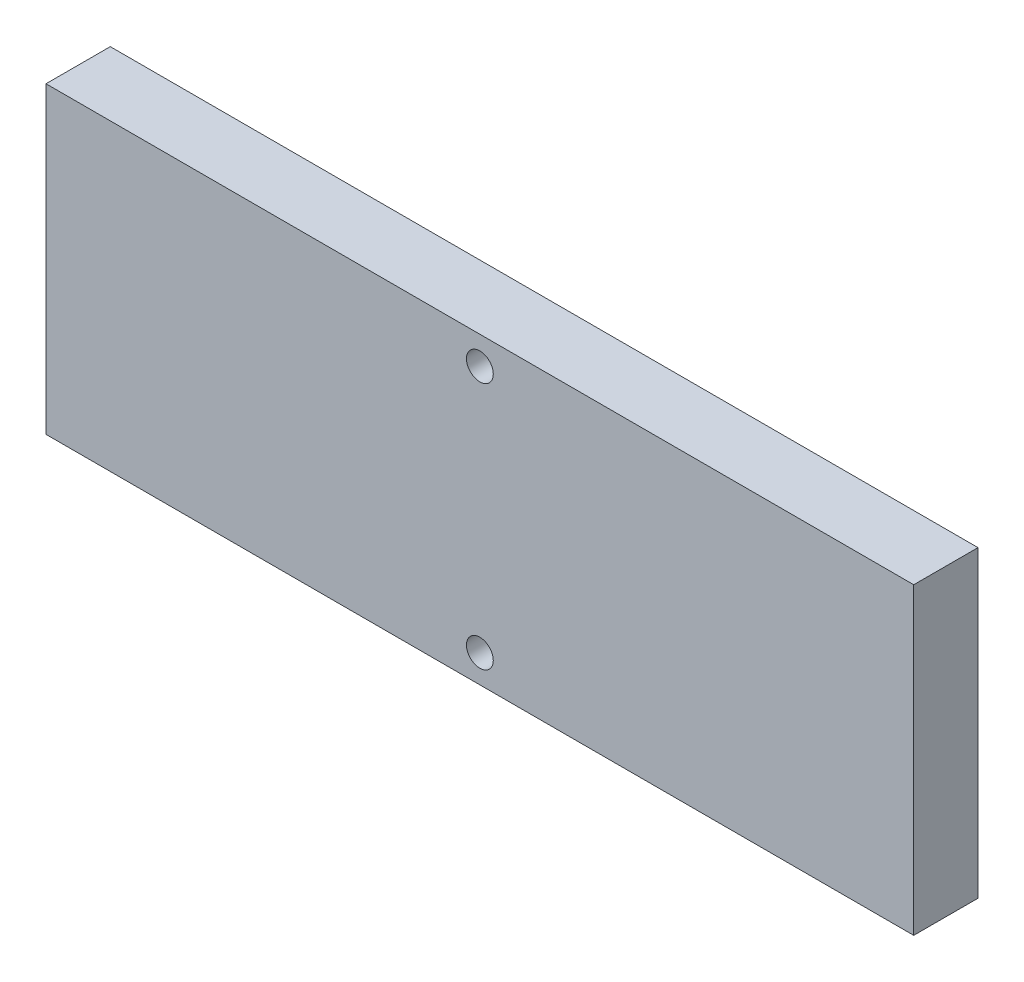
SolidWorks part; units mm, degrees
material "6061-T6 (SS)"
ref_plane "Front Plane" through (0, 0, 0) normal (0, 0, 1) x (1, 0, 0)
ref_plane "Top Plane" through (0, 0, 0) normal (0, 1, 0) x (1, 0, 0)
ref_plane "Right Plane" through (0, 0, 0) normal (1, 0, 0) x (0, 0, -1)
sketch "Sketch1" plane through (0, 0, 0) normal (0, 0, 1) x (1, 0, 0)
  line L1 (-85.725, -30) -> (85.725, -30)
  line L2 (-85.725, -30) -> (-85.725, 30)
  line L3 (-85.725, 30) -> (85.725, 30)
  line L4 (85.725, -30) -> (85.725, 30)
  line L5 (-85.725, -30) -> (85.725, 30) construction
  line L6 (-85.725, 30) -> (85.725, -30) construction
  point P0 (0, 0)
  dimension "D1" = 171.45
  dimension "D2" = 60
extrude "Boss-Extrude1" add sketch "Sketch1" along normal mid plane 12.7
sketch "Sketch2" plane through (0, 0, 6.35) normal (0, 0, 1) x (1, 0, 0)
  line L0 (85.725, 30) -> (-85.725, 30) construction
  line L1 (0, 0) -> (85.725, 0) construction
  line L2 (85.725, -30) -> (85.725, 30) construction
  point P0 (0, 24.5)
  point P8 (0, -24.5)
  dimension "D1" = 5.5
hole_wizard "M5 Clearance Hole1" positions "Sketch3" profile "Sketch4" hole size "M5" standard "ANSI Metric" end condition through all
sketch "Sketch3" plane through (0, 0, 6.35) normal (0, 0, 1) x (1, 0, 0)
  point P0 (0, 24.5)
  point P3 (0, -24.5)
sketch "Sketch4" plane through (0, 24.5, 6.35) normal (1, 0, 0) x (0, -1, 0)
  line L0 (0, 0) -> (0, 12.7)
  line L1 (0, 12.7) -> (2.65, 12.7)
  line L2 (2.65, 12.7) -> (2.65, 0)
  line L5 (2.65, 0) -> (0, 0)
  line L11 (0, -6.35) -> (0, 107.95) construction
  dimension "Thru Hole Dia." = 5.3
  dimension "Thru Hole Depth" = 12.7
equation "\"D1@Sketch1\"=6.75in"
equation "\"D1@Boss-Extrude1\"=0.5in"
